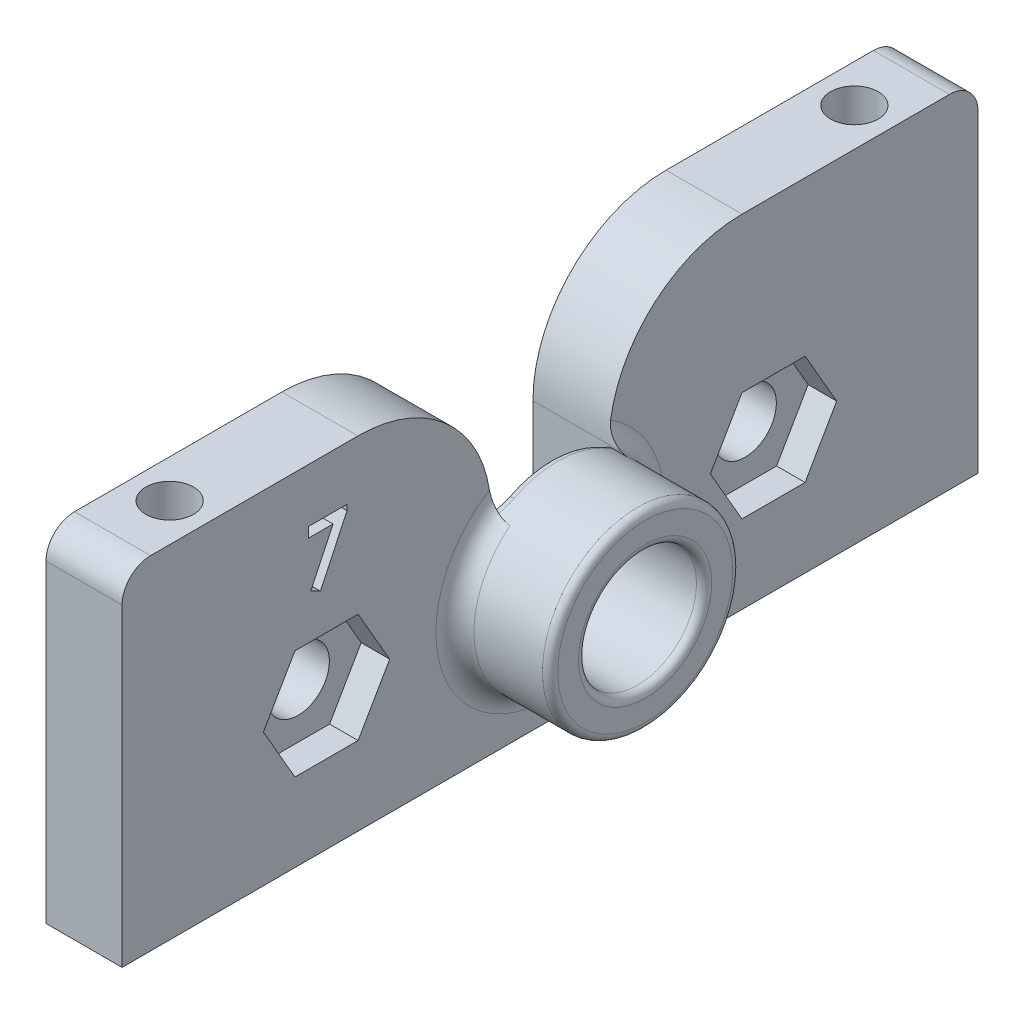
SolidWorks part; units mm, degrees
ref_plane "Front Plane" through (0, 0, 0) normal (0, 0, 1) x (1, 0, 0)
ref_plane "Top Plane" through (0, 0, 0) normal (0, 1, 0) x (1, 0, 0)
ref_plane "Right Plane" through (0, 0, 0) normal (1, 0, 0) x (0, 0, -1)
sketch "Sketch1" plane through (0, 0, 0) normal (1, 0, 0) x (0, 0, -1)
  line L1 (22.5, -9) -> (-22.5, -9)
  line L2 (22.5, -9) -> (22.5, 9)
  line L3 (22.5, 9) -> (-22.5, 9)
  line L4 (-22.5, -9) -> (-22.5, 9)
  line L5 (22.5, -9) -> (-22.5, 9) construction
  line L6 (22.5, 9) -> (-22.5, -9) construction
  point P0 (0, 0)
  dimension "D1" = 45
  dimension "D2" = 18
extrude "Boss-Extrude1" add sketch "Sketch1" along normal blind 4
sketch "Sketch2" plane through (4, 0, 0) normal (1, 0, 0) x (0, 0, -1)
  line L0 (-3.1, -2) -> (-3.1, 9)
  line L1 (22.5, 9) -> (-22.5, 9) construction
  line L2 (3.1, -2) -> (3.1, 9)
  line L3 (-22.5, -9) -> (22.5, -9) construction
  line L4 (3.1, 9) -> (-3.1, 9)
  line L6 (-9.7927, -9) -> (13.6616, -9) construction
  line L7 (-9.7927, -9) -> (-9.7927, -3.5) construction
  line L8 (-9.7927, -3.5) -> (13.6616, -3.5) construction
  line L9 (13.6616, -9) -> (13.6616, -3.5) construction
  circle A0 centre (-11.75, -2) radius 1.65
  arc A8 (-3.1, -2) -> (3.1, -2) centre (0, -2) ccw
  dimension "D3" = 3.3
  dimension "D4" = 6.2
  dimension "D5" = 11.75
  dimension "D2" = 7
  dimension "D1" = 7
  dimension "D6" = 5.5
extrude "Cut-Extrude1" cut sketch "Sketch2" against normal blind 5
mirror "Mirror1" about plane through (0, 0, 0) normal (0, 0, 1) of "Cut-Extrude1"
fillet "Fillet1" radius 1.5 2 edges at (2, 9, -22.5) (2, 9, 22.5)
sketch "Sketch6" plane through (4, 0, 0) normal (1, 0, 0) x (0, 0, -1)
  line L1 (-13.4099, -4.875) -> (-10.0901, -4.875)
  line L2 (-10.0901, -4.875) -> (-8.4302, -2)
  line L3 (-8.4302, -2) -> (-10.0901, 0.875)
  line L4 (-10.0901, 0.875) -> (-13.4099, 0.875)
  line L5 (-13.4099, 0.875) -> (-15.0698, -2)
  line L6 (-15.0698, -2) -> (-13.4099, -4.875)
  line L7 (13.4099, 0.875) -> (10.0901, 0.875)
  line L8 (10.0901, 0.875) -> (8.4302, -2)
  line L9 (8.4302, -2) -> (10.0901, -4.875)
  line L10 (10.0901, -4.875) -> (13.4099, -4.875)
  line L11 (13.4099, -4.875) -> (15.0698, -2)
  line L12 (15.0698, -2) -> (13.4099, 0.875)
  circle A1 centre (-11.75, -2) radius 2.875 construction
  circle A2 centre (11.75, -2) radius 2.875 construction
  dimension "D1" = 5.75
  dimension "D2" = 5.75
extrude "Cut-Extrude3" cut sketch "Sketch6" against normal blind 1.5
sketch "Sketch10" plane through (4, 0, 0) normal (1, 0, 0) x (0, 0, -1)
  line L0 (-3.1, 9) -> (-3.1, -2) construction
  line L1 (3.1, 9) -> (3.1, -2) construction
  arc A0 (-3.1, -2) -> (3.1, -2) centre (0, -2) ccw construction
sketch "Sketch3" plane through (4, 0, 0) normal (1, 0, 0) x (0, 0, -1)
  line L0 (-5, -2) -> (-8.4302, -2) construction
  line L3 (-3.1, -2) -> (-5, -2)
  line L4 (3.1, -2) -> (5, -2)
  line L5 (-10.0901, 0.875) -> (-8.4302, -2) construction
  line L6 (-9.8736, -4.5) -> (-4.3301, -4.5) construction
  line L7 (5, -2) -> (8.4302, -2) construction
  line L8 (-8.4302, -2) -> (-10.0901, 0.875) construction
  line L9 (9.8736, -4.5) -> (4.3301, -4.5) construction
  line L10 (8.4302, -2) -> (5, -2)
  line L11 (-22.5, 7.5) -> (-22.5, -9) construction
  line L12 (-22.5, -9) -> (22.5, -9) construction
  line L13 (-22.5, -9) -> (-22.5, -3.5) construction
  line L14 (-22.5, -3.5) -> (22.5, -3.5) construction
  line L15 (22.5, -9) -> (22.5, -3.5) construction
  line L16 (22.5, -9) -> (22.5, 7.5) construction
  line L17 (-22.5, -9) -> (22.5, -9) construction
  line L18 (-10.0901, -4.875) -> (-8.4302, -2) construction
  line L19 (10, -11.5) -> (-10, -11.5) construction
  line L20 (10, -11.5) -> (10, -3.5) construction
  line L21 (10, -3.5) -> (-10, -3.5) construction
  line L22 (-10, -11.5) -> (-10, -3.5) construction
  line L23 (10, -11.5) -> (-10, -3.5) construction
  line L24 (10, -3.5) -> (-10, -11.5) construction
  line L25 (10.0901, 0.875) -> (8.4302, -2) construction
  line L26 (10.0901, 0.875) -> (8.4302, -2) construction
  line L27 (-8.4302, -2) -> (-9.8736, -4.5) construction
  line L28 (8.4302, -2) -> (10.0901, -4.875) construction
  line L29 (8.4302, -2) -> (9.8736, -4.5) construction
  arc A1 (-5, -2) -> (5, -2) centre (0, -2) ccw
  arc A2 (-3.1, -2) -> (3.1, -2) centre (0, -2) ccw construction
  arc A3 (-3.1, -2) -> (3.1, -2) centre (0, -2) ccw
  arc A4 (-3.1, -2) -> (3.1, -2) centre (0, -2) ccw construction
  point P24 (0, -7.5)
  arc M6 (3.1, -2) -> (-3.1, -2) centre (0, -2) cw
  dimension "D1" = 5.5
  dimension "D2" = 8
  dimension "D3" = 5
  dimension "D4" = 2.5
  dimension "D8" = 20
extrude "Boss-Extrude4" [suppressed] add sketch "Sketch3" along normal blind 5 contours L3 A1 L4 M6
sketch "Sketch16" plane through (4, 0, 0) normal (1, 0, 0) x (0, 0, -1)
  circle A0 centre (0, -2) radius 3.1
  circle A1 centre (0, -2) radius 5
  arc A3 (-3.1, -2) -> (3.1, -2) centre (0, -2) ccw construction
  arc A4 (-5, -2) -> (5, -2) centre (0, -2) ccw construction
  point P4 (-19.5507, 3.876)
  point P6 (0, -2)
  point P10 (-0.1939, -2)
extrude "Boss-Extrude5" add sketch "Sketch16" along normal blind 5
sketch "Sketch11" [suppressed] plane through (0, 0, 0) normal (-1, 0, 0) x (0, 0, 1)
  line L0 (4, -2) -> (-4, -2) construction
  line L2 (-4, -2) -> (-4, 10.093)
  line L4 (-4, 10.093) -> (4, 10.093)
  line L5 (4, 10.093) -> (4, -2)
  circle A0 centre (0, -2) radius 4 construction
  arc A1 (4, -2) -> (-4, -2) centre (0, -2) cw
  dimension "D1" = 8
extrude "Cut-Extrude6" [suppressed] cut sketch "Sketch11" against normal up to surface (4 mm away)
sketch "Sketch4" plane through (0, -9, 0) normal (0, -1, 0) x (1, 0, 0)
  line L0 (2, 22.5) -> (2, -22.5) construction
  line L1 (4, 22.5) -> (0, 22.5) construction
  line L2 (4, -22.5) -> (0, -22.5) construction
  circle A0 centre (2, 18) radius 1.25
  circle A1 centre (2, -18) radius 1.25
  dimension "D1" = 2.5
  dimension "D2" = 2.5
  dimension "D3" = 18
  dimension "D4" = 18
extrude "Cut-Extrude2" cut sketch "Sketch4" against normal up to surface (18 mm away) up to face at (2, 9, 12.05)
fillet "Fillet9" radius 7 2 edges at (2, 9, 3.1) (2, 9, -3.1)
sketch "Sketch13" plane through (4, 0, 0) normal (1, 0, 0) x (0, 0, -1)
  text T0 "<b>7</b>"
extrude "Cut-Extrude7" cut sketch "Sketch13" against normal blind 1
fillet "Fillet18" radius 1 2 edges at (4, -0.0385, -3.1) (4, -0.0385, 3.1)
fillet "Fillet17" radius 1 1 edges at (4, -7, 0)
fillet "Fillet19" radius 0.4 5 edges at (9, -2, -5) (9, -2, -3.1) (3.5341, 2.0403, -2.9454) (3.734, 2.1565, 2.7792) (4, 3, 0)
